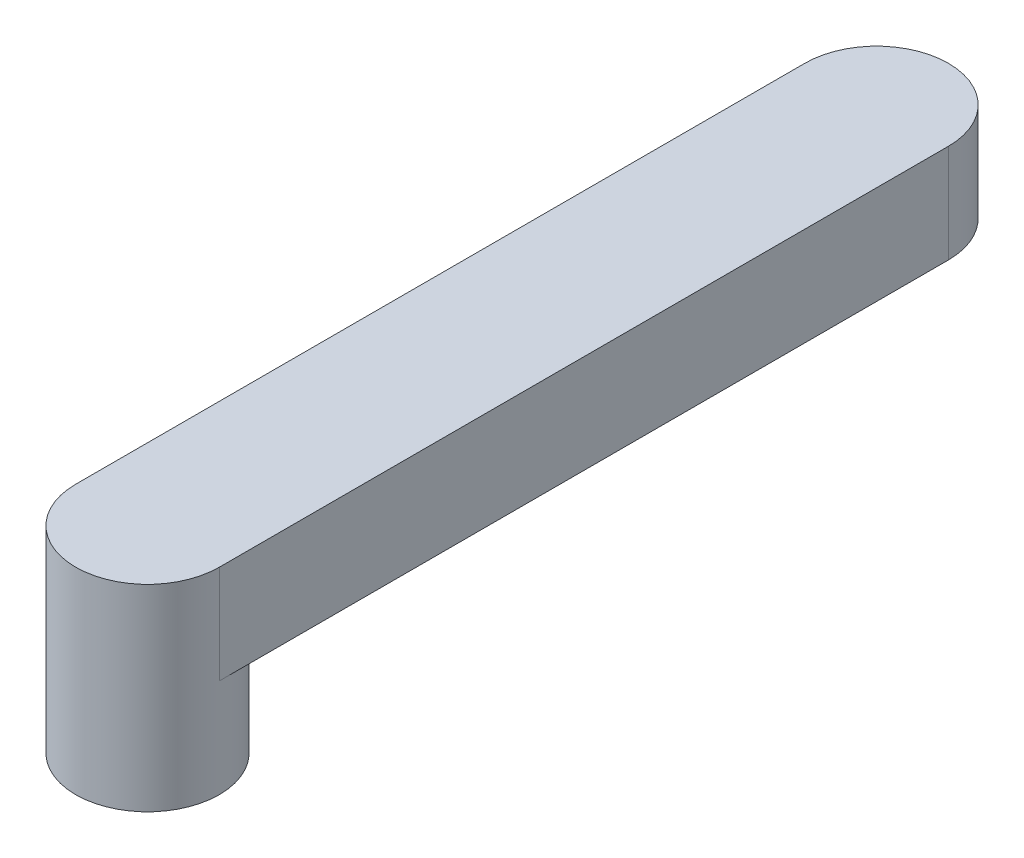
SolidWorks part; units mm, degrees
ref_plane "Front Plane" through (0, 0, 0) normal (0, 0, 1) x (1, 0, 0)
ref_plane "Top Plane" through (0, 0, 0) normal (0, 1, 0) x (1, 0, 0)
ref_plane "Right Plane" through (0, 0, 0) normal (1, 0, 0) x (0, 0, -1)
sketch "Sketch1" plane through (0, 0, 0) normal (0, 1, 0) x (1, 0, 0)
  line L0 (0, 0) -> (0, -12.3979) construction
  line L1 (3.175, 0) -> (3.175, -12.3979)
  line L2 (-3.175, 0) -> (-3.175, -12.3979)
  line L3 (0, -12.3979) -> (0, 10.16) construction
  line L4 (-2.2225, -12.3979) -> (-2.2225, 10.16)
  line L5 (2.2225, -12.3979) -> (2.2225, 10.16)
  arc A0 (3.175, 0) -> (-3.175, 0) centre (0, 0) ccw
  arc A1 (-3.175, -12.3979) -> (3.175, -12.3979) centre (0, -12.3979) ccw
  arc A2 (-2.2225, -12.3979) -> (2.2225, -12.3979) centre (0, -12.3979) ccw
  arc A3 (2.2225, 10.16) -> (-2.2225, 10.16) centre (0, 10.16) ccw
  circle A4 centre (0, -12.3979) radius 2.2225
  point P3 (0, -6.199)
  point P10 (0, -1.119)
  dimension "D2" = 6.35
  dimension "D4" = 4.445
extrude "Boss-Extrude1" add sketch "Sketch1" along normal blind 3.048 contours L5 A3 L4 A0 | A4 L5 A0 L4 region at (0, 0, -7.4087) region at (0, 0, 3.8866)
extrude "Boss-Extrude2" add sketch "Sketch1<3>" along normal mid plane 6.096 contours A2 A4 region at (0, 0, 12.3979)
sketch "Sketch1<3>" plane through (0, 0, 0) normal (0, 1, 0) x (1, 0, 0) same geometry as "Sketch1"
